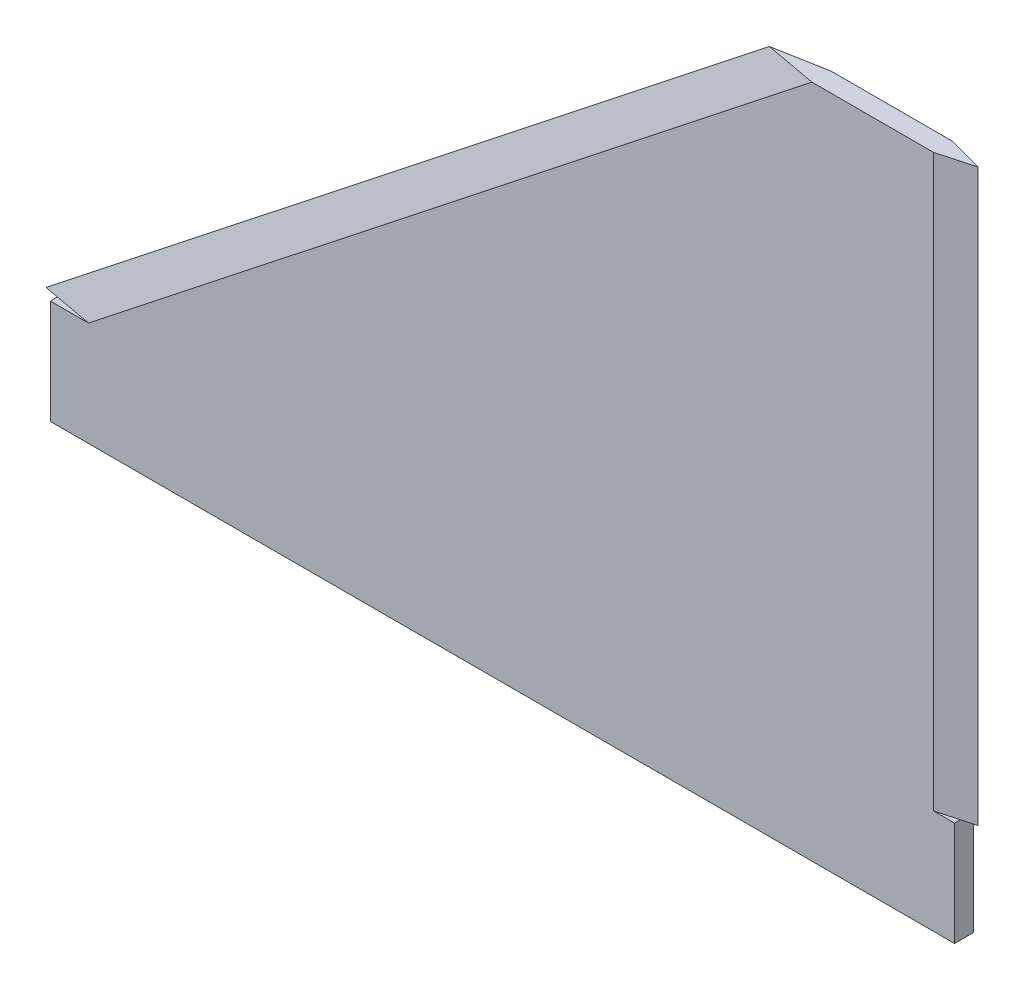
SolidWorks part; units mm, degrees
material "Hexcel AS4C (3000 Filaments)"
ref_plane "Front Plane" through (0, 0, 0) normal (0, 0, 1) x (1, 0, 0)
ref_plane "Top Plane" through (0, 0, 0) normal (0, 1, 0) x (1, 0, 0)
ref_plane "Right Plane" through (0, 0, 0) normal (1, 0, 0) x (0, 0, -1)
sketch "Sketch1" plane through (0, 0, 0) normal (0, 0, 1) x (1, 0, 0)
  line L0 (-130, 0) -> (-134, 0)
  line L1 (-130, -30) -> (130, -30)
  line L2 (-130, -30) -> (-130, 0)
  line L4 (130, -30) -> (130, 0)
  line L5 (-134, 0) -> (74, 164)
  line L6 (74, 164) -> (134, 164)
  line L7 (134, 164) -> (134, 0)
  line L8 (134, 0) -> (130, 0)
  line L9 (-130, 0) -> (130, 0)
  dimension "D1" = 30
  dimension "D2" = 268
  dimension "D3" = 260
  dimension "D4" = 164
  dimension "D5" = 60
extrude "Boss-Extrude1" add sketch "Sketch1" along normal blind 2.75 and the other way blind 2.75 contours L9 L2 L1 L4 | L0 L9 L8 L7 L6 L5 region at (0, -15, 0) region at (41.0081, 64.6667, 0)
sketch "Sketch2" plane through (0, 164, 0) normal (0, 1, 0) x (1, 0, 0)
  line L0 (74, 0) -> (89, -2.75)
  line L1 (74, 2.75) -> (74, -2.75) construction
  line L2 (74, -2.75) -> (134, -2.75) construction
  line L3 (89, -2.75) -> (74, -2.75)
  line L4 (74, -2.75) -> (74, 0)
  line L5 (74, 2.75) -> (74, 0)
  line L6 (89, 2.75) -> (74, 0)
  line L7 (74, 2.75) -> (134, 2.75) construction
  line L8 (74, 2.75) -> (89, 2.75)
  line L9 (89, 2.75) -> (89, -2.75) construction
  line M3 (74, 2.75) -> (74, -2.75)
  line M4 (74, -2.75) -> (134, -2.75)
  line M6 (134, 2.75) -> (74, 2.75)
  dimension "D1" = 15
extrude "Cut-Extrude1" cut sketch "Sketch2" along direction (0.7853, 0.6192, 0) on the side against the normal up to surface (164 mm away) contours L0 M3 M4 | L6 M6 M3 region at (79, 164, 1.8333) region at (79, 164, -1.8333) up to face at (132, 0, 0)
sketch "Sketch3" plane through (0, 164, 0) normal (0, 1, 0) x (1, 0, 0)
  line L0 (124, 2.75) -> (134, 2.75)
  line L1 (89, 2.75) -> (134, 2.75) construction
  line L2 (134, -2.75) -> (134, 0)
  line L3 (134, -2.75) -> (124, -2.75)
  line L4 (89, -2.75) -> (134, -2.75) construction
  line L5 (124, -2.75) -> (134, 0)
  line L6 (134, 0) -> (124, 2.75)
  line L7 (124, 2.75) -> (124, -2.75) construction
  line L8 (134, 2.75) -> (134, 0)
  line M5 (89, -2.75) -> (134, -2.75)
  line M6 (134, -2.75) -> (134, 2.75)
  line M7 (134, 2.75) -> (89, 2.75)
  dimension "D1" = 10
extrude "Cut-Extrude2" cut sketch "Sketch3" against normal up to surface (164 mm away) contours L5 M5 M6 | L6 M6 M7 region at (130.6667, 164, 1.8333) region at (130.6667, 164, -1.8333) up to face at (132, 0, 0)
sketch "Sketch4" plane through (0, 0, 2.75) normal (0, 0, 1) x (1, 0, 0)
  line L0 (-134, 0) -> (134, 0)
  line L1 (74, 164) -> (134, 164)
  line L2 (104, 164) -> (0, 0)
  dimension "D1" = 194.1958
